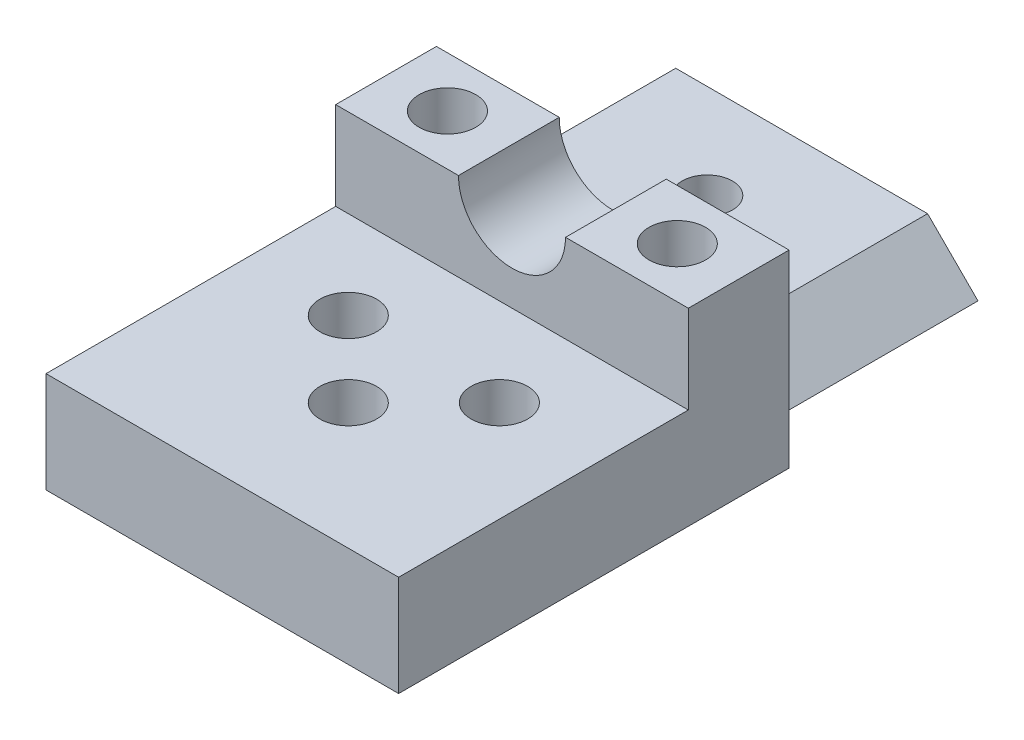
SolidWorks part; units mm, degrees
ref_plane "Front Plane" through (0, 0, 0) normal (0, 0, 1) x (1, 0, 0)
ref_plane "Top Plane" through (0, 0, 0) normal (0, 1, 0) x (1, 0, 0)
ref_plane "Right Plane" through (0, 0, 0) normal (1, 0, 0) x (0, 0, -1)
sketch "Sketch1" plane through (0, 0, 0) normal (0, 1, 0) x (1, 0, 0)
  line L1 (0, 0) -> (28, 0)
  line L2 (0, 0) -> (0, 46)
  line L3 (0, 46) -> (28, 46)
  line L4 (28, 0) -> (28, 46)
  circle A3 centre (14, 38.5) radius 2
  dimension "D9" = 4
  dimension "D1" = 28
  dimension "D7" = 46
  dimension "D8" = 7.5
  dimension "D2" = 14
extrude "Boss-Extrude1" add sketch "Sketch1" along normal blind 8
sketch "Sketch6" plane through (0, 8, 0) normal (0, 1, 0) x (1, 0, 0)
  line L0 (0, 46) -> (0, 0) construction
  line L1 (0, 0) -> (28, 0) construction
  circle A0 centre (8, 16) radius 2.25
  circle A1 centre (19.997, 16) radius 2.25
  circle A2 centre (14, 10) radius 2.25
  dimension "D5" = 4.5
  dimension "D1" = 6
  dimension "D2" = 11.997
  dimension "D3" = 8
  dimension "D4" = 16
  dimension "D6" = 6
extrude "DragChainMountHolesCut-Extrude1" cut sketch "Sketch6" against normal blind 4
sketch "Sketch2" plane through (0, 8, 0) normal (0, 1, 0) x (1, 0, 0)
  line L0 (28, 0) -> (28, 46) construction
  line L1 (0, 31) -> (28, 31)
  line L2 (0, 31) -> (0, 23)
  line L3 (0, 23) -> (28, 23)
  line L4 (28, 31) -> (28, 23)
  line L5 (0, 46) -> (0, 0) construction
  line L6 (28, 46) -> (0, 46) construction
  dimension "D2" = 15
extrude "BridgeBoss-Extrude2" add sketch "Sketch2" along normal blind 7
sketch "Sketch3" plane through (0, 0, -23) normal (0, 0, 1) x (1, 0, 0)
  line L0 (0, 15) -> (28, 15) construction
  line L2 (9.75, 15) -> (18.25, 15)
  line L3 (0, 15) -> (0, 8) construction
  arc A0 (18.25, 15) -> (9.75, 15) centre (14, 15) cw
  dimension "D2" = 14
  dimension "D1" = 8.5
extrude "GrommetCut-Extrude3" cut sketch "Sketch3" against normal through all
sketch "BridgeMountHolesSketch4" plane through (0, 15, 0) normal (0, 1, 0) x (1, 0, 0)
  line L0 (0, 31) -> (9.75, 23) construction
  line L1 (18.25, 31) -> (28, 23) construction
  line L2 (0, 31) -> (0, 23) construction
  line L3 (28, 23) -> (28, 31) construction
  line L4 (9.75, 31) -> (9.75, 23) construction
  circle A0 centre (4.875, 27) radius 2.25
  circle A1 centre (23.125, 27) radius 2.25
  point P14 (0, 27)
  dimension "D1" = 4.5
  dimension "D2" = 18.25
  dimension "D3" = 28
  dimension "D4" = 18.25
  dimension "D5" = 4.875
  dimension "D6" = 9.75
extrude "BridgeMountholesCut-Extrude4" cut sketch "BridgeMountHolesSketch4" against normal blind 4
sketch "Sketch5" plane through (0, 0, 0) normal (-1, 0, 0) x (0, 0, 1)
  line L1 (-46, 0) -> (-31, 0)
  line L2 (-46, 0) -> (-46, 4)
  line L3 (-46, 4) -> (-31, 4)
  line L4 (-31, 0) -> (-31, 4)
  dimension "D1" = 15
  dimension "D2" = 4
extrude "EdgeCut-Extrude5" cut sketch "Sketch5" against normal through all
chamfer "Chamfer1" distance 4 angle 45 2 edges at (28, 8, -38.5) (0, 8, -38.5)
equation "\"DragChainHeight\"= 28mm"
equation "\"D1@Sketch1\"=\"DragChainHeight\""
equation "\"BuildPlateMountHoleOffsetFromEdge\"= 7.5mm"
equation "\"D8@Sketch1\"=\"BuildPlateMountHoleOffsetFromEdge\""
equation "\"DragChainBridgeHeight\"= 7mm"
equation "\"DragChainBuildPlateHolderWidth\"= \"DragChainWidth\" + \"DragChainBuildPlateBridgeWidth\" + \"BuildPlateMountHoleOffsetFromEdge\" * 2"
equation "\"DragChainBuildPlateBridgeWidth\"= 8mm"
equation "\"D7@Sketch1\"=\"DragChainBuildPlateHolderWidth\""
equation "\"D1@Sketch2\"=\"DragChainBuildPlateBridgeWidth\""
equation "\"D2@Sketch2\"=\"BuildPlateMountHoleOffsetFromEdge\"*2"
equation "\"M4HoleDiameter\"=4"
equation "\"M5HoleDiameter\"=5"
equation "\"D9@Sketch1\"=\"M4HoleDiameter\""
equation "\"DragChainWidth\"= 23mm"
equation "\"D1@BridgeBoss-Extrude2\"=\"DragChainBridgeHeight\""
equation "\"D1@Sketch5\"=\"BuildPlateMountHoleOffsetFromEdge\" * 2"
equation "\"M3HeatInsertDiameter\"=4.5"
equation "\"D5@Sketch6\"=\"M3HeatInsertDiameter\""
equation "\"D2@Sketch1\"=\"DragChainHeight\"/2"
equation "\"D2@Sketch3\"=\"DragChainHeight\"/2"
equation "\"GrommetHoleDiameter\"=8.5"
equation "\"D1@Sketch3\"=\"GrommetHoleDiameter\""
